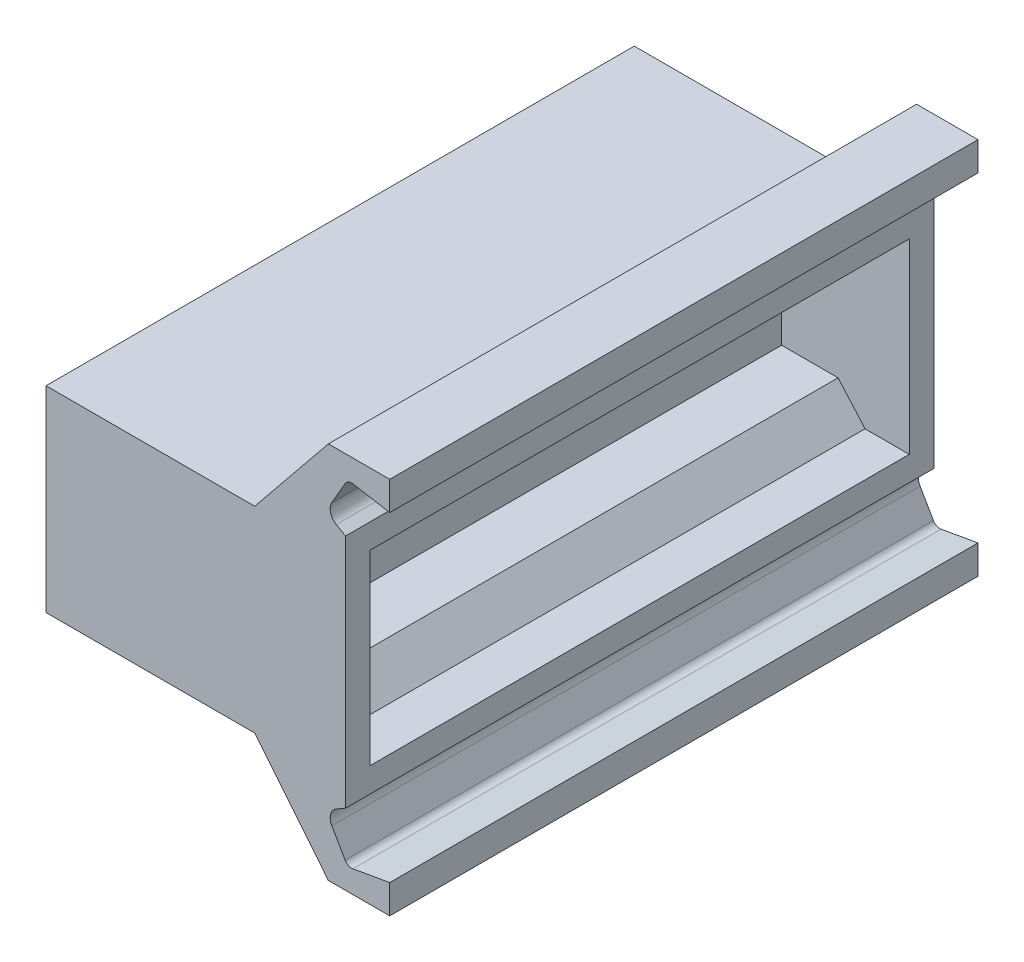
SolidWorks part; units mm, degrees
material "ABS"
ref_plane "Plan de face" through (0, 0, 0) normal (0, 0, 1) x (1, 0, 0)
ref_plane "Plan de dessus" through (0, 0, 0) normal (0, 1, 0) x (1, 0, 0)
ref_plane "Plan de droite" through (0, 0, 0) normal (1, 0, 0) x (0, 0, -1)
sketch "Esquisse1" plane through (0, 0, 0) normal (0, 0, 1) x (1, 0, 0)
  line L0 (0, 4) -> (0, 2.5)
  line L1 (0, -2.5) -> (0, -4)
  line L2 (0, -4) -> (8.5001, -4)
  line L3 (14, 0) -> (0, 0) construction
  line L4 (8.5001, 4) -> (0, 4)
  line L5 (12.2, 4.8) -> (12.2, 3.8001)
  line L6 (12.2, -3.8) -> (12.2, -4.7999)
  line L7 (0, 2.5) -> (0, -2.5) construction
  line L8 (14, 6.525) -> (14, -6.525) construction
  line L24 (4.8, 2.5) -> (4.8, -2.5)
  line L26 (0, -2.5) -> (4.8, -2.5)
  line L27 (4.8, 2.5) -> (0, 2.5)
  line L28 (14, -6.525) -> (14, -7.7)
  line L29 (8.5001, -4) -> (11.5, -7.7)
  line L30 (11.5, -7.7) -> (14, -7.7)
  line L31 (7, 2.5501) -> (7, -2.5499)
  line L33 (10.3999, -3.8) -> (12.2, -3.8)
  line L34 (9.3, -2.5499) -> (10.3999, -3.8)
  line L35 (7, -2.5499) -> (9.3, -2.5499)
  line L36 (12.4985, -6.7896) -> (14, -6.525)
  line L37 (12.2, -4.7999) -> (11.8201, -5.0191)
  line L38 (12.1865, -6.6441) -> (11.6414, -5.6996)
  line L39 (10.3999, 3.8001) -> (12.2, 3.8001)
  line L40 (8.5001, 4) -> (11.5, 7.7)
  line L41 (9.3, 2.5501) -> (7, 2.5501)
  line L42 (9.3, 2.5501) -> (10.3999, 3.8001)
  line L43 (11.6414, 5.6998) -> (12.1866, 6.6442)
  line L44 (11.8244, 5.0169) -> (12.2, 4.8)
  line L45 (14, 7.7) -> (11.5, 7.7)
  line L46 (14, 6.525) -> (12.4984, 6.7897)
  line L47 (14, 7.7) -> (14, 6.525)
  arc A0 (12.1865, -6.6441) -> (12.4985, -6.7896) centre (12.4463, -6.4942) ccw
  arc A1 (11.8201, -5.0191) -> (11.6414, -5.6996) centre (12.0744, -5.4496) ccw
  arc A2 (11.6414, 5.6998) -> (11.8244, 5.0169) centre (12.0744, 5.4499) ccw
  arc A3 (12.4984, 6.7897) -> (12.1866, 6.6442) centre (12.4464, 6.4942) ccw
  point P0 (0, 0)
  point P1 (14, 0)
  dimension "D1" = 8
  dimension "D2" = 1.5
  dimension "D3" = 1.5
  dimension "D4" = 4.8
  dimension "D5" = 2.2
  dimension "D6" = 14
  dimension "D7" = 5.1
  dimension "D8" = 2.3
  dimension "D9" = 15.4
extrude "Boss.-Extru.1" add sketch "Esquisse1" along normal blind 11.98 and the other way blind 11.98
sketch "Esquisse4" plane through (0, 0, 11.98) normal (0, 0, 1) x (1, 0, 0)
  line L0 (10.3999, 3.8001) -> (12.2, 3.8001) construction
  line L1 (9.3, 2.5501) -> (10.3999, 3.8001) construction
  line L2 (7, 2.5501) -> (9.3, 2.5501) construction
  line L4 (9.3, -2.5499) -> (7, -2.5499) construction
  line L5 (10.3999, -3.8) -> (9.3, -2.5499) construction
  line L6 (12.2, -3.8) -> (10.3999, -3.8) construction
  line L7 (10.3999, 3.8001) -> (12.2, 3.8001)
  line L8 (9.3, 2.5501) -> (10.3999, 3.8001)
  line L9 (7, 2.5501) -> (9.3, 2.5501)
  line L10 (7, 2.5501) -> (0, 2.5)
  line L11 (9.3, -2.5499) -> (7, -2.5499)
  line L12 (10.3999, -3.8) -> (9.3, -2.5499)
  line L13 (12.2, -3.8) -> (10.3999, -3.8)
  line L14 (12.2, 3.8001) -> (12.2, -3.8)
  line L15 (0, 2.5) -> (0, -2.5)
  line L16 (0, -2.5) -> (7, -2.5499)
extrude "Boss.-Extru.2" add sketch "Esquisse4" against normal blind 1
mirror "Symétrie1" about plane through (0, 0, 0) normal (0, 0, 1) of "Boss.-Extru.2"
sketch "Esquisse3" plane through (7, 0, 0) normal (1, 0, 0) x (0, 0, -1)
  circle A0 centre (0, 0) radius 1.4
  circle A1 centre (-5.08, 0) radius 1.4
  circle A2 centre (5.08, 0) radius 1.4
  dimension "D3" = 2.8
  dimension "D1" = 5.08
  dimension "D2" = 5.08
extrude "Enlèv. mat.-Extru.1" cut sketch "Esquisse3" against normal through all
